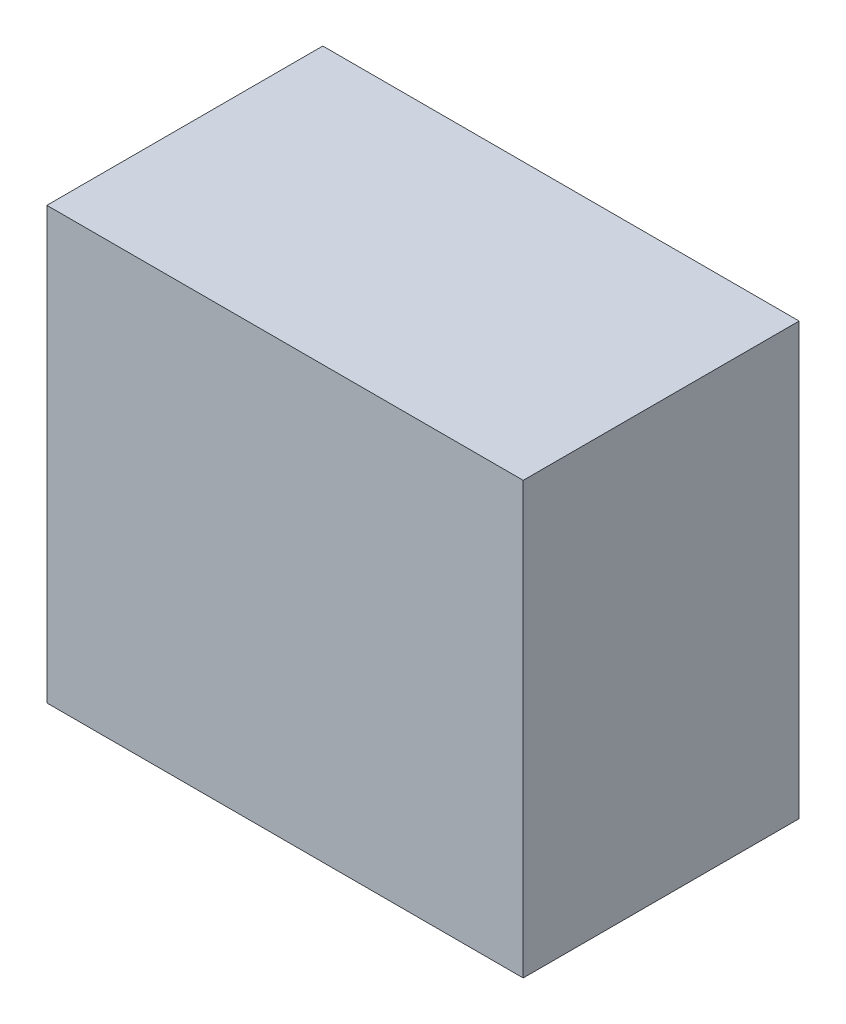
SolidWorks part; units mm, degrees
material "1060 Alloy"
ref_plane "Front" through (0, 0, 0) normal (0, 0, 1) x (1, 0, 0)
ref_plane "Top" through (0, 0, 0) normal (0, 1, 0) x (1, 0, 0)
ref_plane "Right" through (0, 0, 0) normal (1, 0, 0) x (0, 0, -1)
sketch "Sketch3" plane through (0, 0, 0) normal (0, 0, 1) x (1, 0, 0)
  line L0 (-0.127, -6.35) -> (30.1755, -6.35)
  line L1 (0, 0) -> (21.9242, 0)
  line L2 (0, 0) -> (0, -19.8376)
  line L3 (0, -19.8376) -> (21.9242, -19.8376)
  line L4 (21.9242, 0) -> (21.9242, -19.8376)
  line L5 (15.5742, -19.8376) -> (15.5742, 0) construction
  line L6 (15.5742, -6.35) -> (8.0621, -19.3614) construction
  line L15 (12.5496, -11.5887) -> (15.5742, -13.335) construction
  circle A0 centre (15.5742, -6.35) radius 6.0492 construction
  point P14 (0, -6.35)
  point P17 (9.525, -6.35)
  point P20 (7.7871, -19.8376)
  dimension "D2" = 6.35
  dimension "D6" = 3.4925
  dimension "D3" = 60
  dimension "D1" = 9.525
  dimension "D4" = 9.525
  dimension "D5" = 6.35
extrude "Boss-Extrude1" add sketch "Sketch3" along normal mid plane 12.7
sketch "Sketch4" plane through (0, 0, 0) normal (-1, 0, 0) x (0, 0, 1)
  circle A0 centre (0, -6.35) radius 3.175
  dimension "D1" = 6.35
extrude "Cut-Extrude1" cut sketch "Sketch4" against normal blind 9.525
ref_plane "Plane1" through (7.7871, -19.8376, 0) normal (-0.5, -0.866, 0) x (-0.866, 0.5, 0)
ref_plane "Mirror Plane" through (15.5742, 0, 0) normal (-1, 0, 0) x (0, 0, 1)
sketch "Sketch5" plane through (7.7871, -19.8376, 0) normal (-0.5, -0.866, 0) x (-0.866, 0.5, 0)
  circle A0 centre (0, 0) radius 3.175
  dimension "D1" = 6.35
extrude "Cut-Extrude5" cut sketch "Sketch5" against normal blind 9.525 and the other way up to next
sketch "Sketch6" plane through (0, 0, -6.35) normal (0, 0, -1) x (-1, 0, 0)
  circle A0 centre (-15.5742, -6.35) radius 3.175
  dimension "D1" = 6.35
extrude "Cut-Extrude6" cut sketch "Sketch6" against normal blind 9.525
equation "\"truss_member_od\"= .25in"
equation "\"truss_member_id\"= 0in"
equation "\"truss_member_L1\"= 2.125in"
equation "\"connector_hole_depth\"= .375in"
equation "\"D1@Boss-Extrude1\"=\"truss_member_od\"*2"
equation "\"D6@Sketch3\"=\"truss_member_od\"/2*1.1"
equation "\"D1@Sketch4\"=\"truss_member_od\""
equation "\"D1@Cut-Extrude1\"=\"connector_hole_depth\""
equation "\"D1@Sketch3\"=\"connector_hole_depth\""
equation "\"D4@Sketch3\"=\"connector_hole_depth\""
equation "\"D1@Sketch5\"=\"truss_member_od\""
equation "\"D1@Cut-Extrude5\"=\"connector_hole_depth\""
equation "\"D1@Cut-Extrude6\"=\"connector_hole_depth\""
equation "\"D1@Sketch6\"=\"truss_member_od\""
equation "\"D5@Sketch3\"=\"truss_member_od\""
